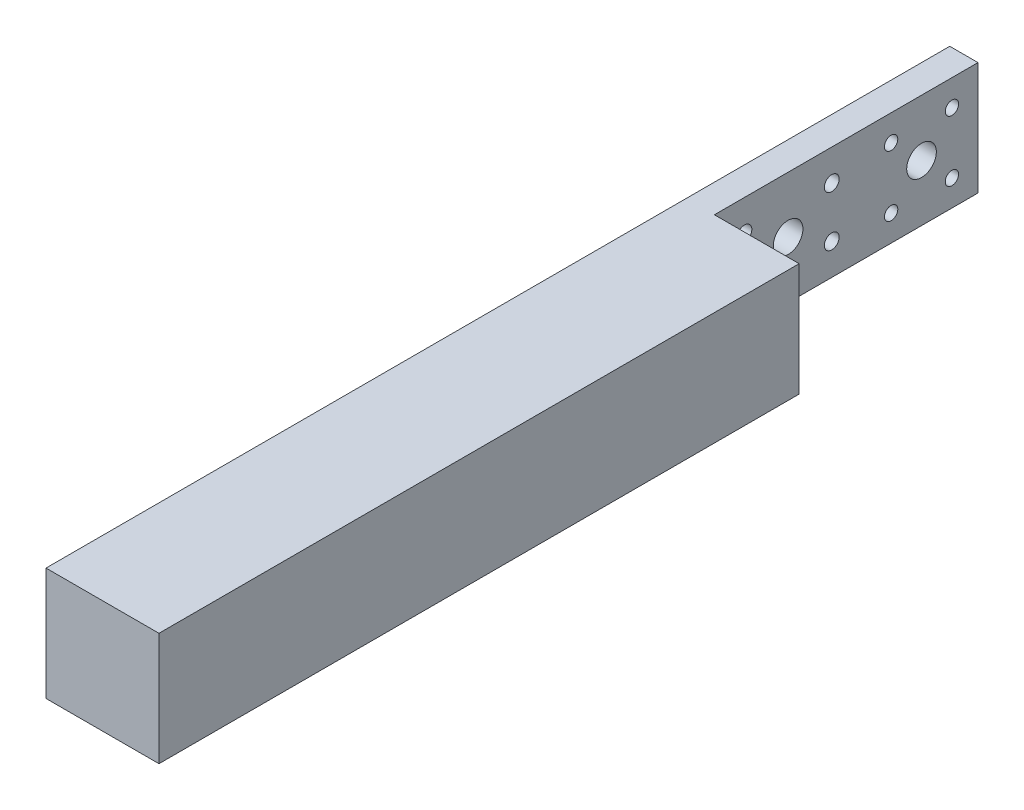
SolidWorks part; units mm, degrees
material "PE High Density"
ref_plane "Front Plane" through (0, 0, 0) normal (0, 0, 1) x (1, 0, 0)
ref_plane "Top Plane" through (0, 0, 0) normal (0, 1, 0) x (1, 0, 0)
ref_plane "Right Plane" through (0, 0, 0) normal (1, 0, 0) x (0, 0, -1)
sketch "Sketch1" plane through (0, 0, 0) normal (0, 0, 1) x (1, 0, 0)
  line L1 (-19.05, 19.05) -> (19.05, 19.05)
  line L2 (-19.05, 19.05) -> (-19.05, -19.05)
  line L3 (-19.05, -19.05) -> (19.05, -19.05)
  line L4 (19.05, 19.05) -> (19.05, -19.05)
  line L5 (-19.05, 19.05) -> (19.05, -19.05) construction
  line L6 (-19.05, -19.05) -> (19.05, 19.05) construction
  point P0 (0, 0)
  dimension "D1" = 38.1
  dimension "D2" = 38.1
extrude "Boss-Extrude1" add sketch "Sketch1" along normal blind 304.8
sketch "Sketch2" plane through (19.05, 0, 0) normal (1, 0, 0) x (0, 0, -1)
  line L0 (-304.8, 0) -> (0, 0) construction
  line L1 (-304.8, -19.05) -> (-304.8, 19.05) construction
  line L2 (0, -19.05) -> (0, 19.05) construction
  circle A0 centre (-19.05, 0) radius 5
  circle A1 centre (-64.05, 0) radius 5
  dimension "D1" = 10
  dimension "D2" = 45
  dimension "D3" = 19.05
extrude "Cut-Extrude1" cut sketch "Sketch2" against normal through all
sketch "Sketch4" plane through (19.05, 0, 0) normal (1, 0, 0) x (0, 0, -1)
  line L1 (-64.05, 17) -> (-78.7724, 8.5) construction
  line L2 (-78.7724, 8.5) -> (-78.7724, -8.5) construction
  line L3 (-78.7724, -8.5) -> (-64.05, -17) construction
  line L4 (-64.05, -17) -> (-49.3276, -8.5) construction
  line L5 (-49.3276, -8.5) -> (-49.3276, 8.5) construction
  line L6 (-49.3276, 8.5) -> (-64.05, 17) construction
  circle A0 centre (-64.05, 0) radius 17 construction
  circle A2 centre (-64.05, 0) radius 14.7224 construction
  circle A3 centre (-78.7724, 8.5) radius 2.5
  dimension "D1" = 34
  dimension "D3" = 5
extrude "Cut-Extrude3" cut sketch "Sketch4" against normal through all
pattern_circular "CirPattern2" count 6 over 360 about axis through (-19.05, 0, 64.05) along (1, 0, 0) skipping 2, 5 of "Cut-Extrude3"
sketch "Sketch5" plane through (19.05, 0, 0) normal (1, 0, 0) x (0, 0, -1)
  line L1 (-29.303, -10.253) -> (-8.797, -10.253) construction
  line L2 (-29.303, -10.253) -> (-29.303, 10.253) construction
  line L3 (-29.303, 10.253) -> (-8.797, 10.253) construction
  line L4 (-8.797, -10.253) -> (-8.797, 10.253) construction
  line L5 (-29.303, -10.253) -> (-8.797, 10.253) construction
  line L6 (-29.303, 10.253) -> (-8.797, -10.253) construction
  circle A0 centre (-29.303, 10.253) radius 2.25
  point P0 (-19.05, 0)
  dimension "D2" = 4.5
  dimension "D1" = 29
extrude "Cut-Extrude4" cut sketch "Sketch5" against normal through all
pattern_circular "CirPattern3" count 4 over 360 about axis through (-19.05, 0, 19.05) along (1, 0, 0) of "Cut-Extrude4"
sketch "Sketch6" plane through (19.05, 0, 0) normal (1, 0, 0) x (0, 0, -1)
  line L0 (-304.8, -19.05) -> (0, -19.05) construction
  line L1 (0, 19.05) -> (-88.9, 19.05)
  line L2 (0, 19.05) -> (0, -19.05)
  line L3 (0, -19.05) -> (-88.9, -19.05)
  line L4 (-88.9, 19.05) -> (-88.9, -19.05)
  dimension "D1" = 88.9
extrude "Cut-Extrude5" cut sketch "Sketch6" against normal blind 28.575
